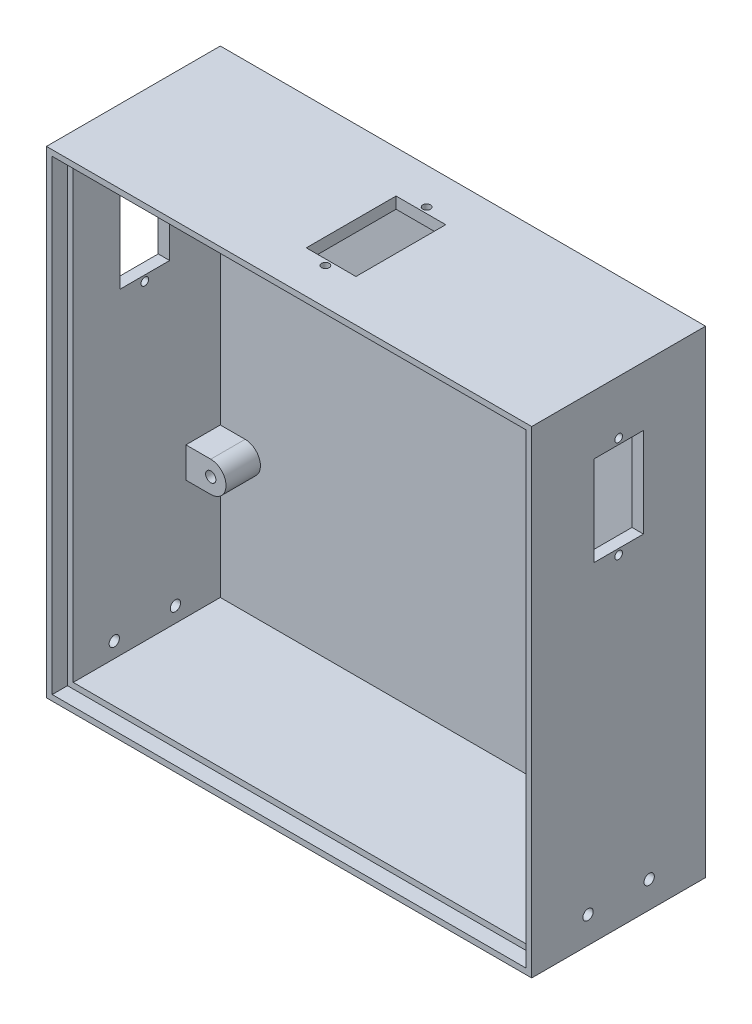
SolidWorks part; units mm, degrees
ref_plane "Front Plane" through (0, 0, 0) normal (0, 0, 1) x (1, 0, 0)
ref_plane "Top Plane" through (0, 0, 0) normal (0, 1, 0) x (1, 0, 0)
ref_plane "Right Plane" through (0, 0, 0) normal (1, 0, 0) x (0, 0, -1)
sketch "Sketch1" plane through (0, 0, 0) normal (0, 0, 1) x (1, 0, 0)
  line L1 (63.5, 62.5) -> (-63.5, 62.5)
  line L2 (63.5, 62.5) -> (63.5, -62.5)
  line L3 (63.5, -62.5) -> (-63.5, -62.5)
  line L4 (-63.5, 62.5) -> (-63.5, -62.5)
  line L5 (63.5, 62.5) -> (-63.5, -62.5) construction
  line L6 (63.5, -62.5) -> (-63.5, 62.5) construction
  point P0 (0, 0)
  dimension "D1" = 127
  dimension "D2" = 125
extrude "Boss-Extrude1" add sketch "Sketch1" along normal blind 45.5
sketch "Sketch2" plane through (0, 0, 45.5) normal (0, 0, 1) x (1, 0, 0)
  line L0 (-63.5, 62.5) -> (-63.5, -62.5) construction
  line L1 (60.5, 59.5) -> (-60.5, 59.5)
  line L2 (60.5, 59.5) -> (60.5, -59.5)
  line L3 (60.5, -59.5) -> (-60.5, -59.5)
  line L4 (-60.5, 59.5) -> (-60.5, -59.5)
  line L5 (60.5, 59.5) -> (-60.5, -59.5) construction
  line L6 (60.5, -59.5) -> (-60.5, 59.5) construction
  line L7 (63.5, 62.5) -> (-63.5, 62.5) construction
  line L9 (62, 61) -> (-62, 61)
  line L10 (62, 61) -> (62, -61)
  line L11 (62, -61) -> (-62, -61)
  line L12 (-62, 61) -> (-62, -61)
  line L13 (62, 61) -> (-62, -61) construction
  line L14 (62, -61) -> (-62, 61) construction
  point P0 (0, 0)
  point P10 (0, 0)
  dimension "D1" = 3
  dimension "D2" = 3
  dimension "D3" = 1.5
  dimension "D4" = 1.5
extrude "Cut-Extrude1" cut sketch "Sketch2" against normal offset from surface (42.5 mm away) 3 contours L1 L4 L3 L2 region at (0, 0, 45.5) up to face at (0, 0, 0)
extrude "Cut-Extrude2" cut sketch "Sketch2<3>" against normal blind 4
sketch "Sketch2<3>" plane through (0, 0, 45.5) normal (0, 0, 1) x (1, 0, 0) same geometry as "Sketch2"
sketch "Sketch3" plane through (0, 0, 3) normal (0, 0, 1) x (1, 0, 0)
  line L0 (35, 53) -> (35, 59.5)
  line L1 (60.5, 59.5) -> (-60.5, 59.5) construction
  line L2 (43, 53) -> (43, 59.5)
  line L3 (60.5, 59.5) -> (-60.5, 59.5) construction
  line L4 (0, -25.025) -> (0, 25.025) construction
  arc A0 (35, 53) -> (43, 53) centre (39, 53) ccw
  circle A2 centre (39, 53) radius 1.35
  line M3 (60.5, 59.5) -> (-60.5, 59.5)
  dimension "D2" = 4
  dimension "D3" = 2.7
  dimension "D1" = 6.5
  dimension "D4" = 39
extrude "Boss-Extrude2" add sketch "Sketch3" along normal blind 9 contours L0 A0 L2 A2 M3 region at (39, 54.7692, 3)
mirror "Mirror1" about plane through (0, 0, 0) normal (1, 0, 0) of "Boss-Extrude2"
sketch "Sketch4" plane through (0, 0, 3) normal (0, 0, 1) x (1, 0, 0)
  line L0 (54, -20.4) -> (60.5, -20.4)
  line L1 (60.5, 59.5) -> (60.5, -59.5) construction
  line L2 (54, -28.4) -> (60.5, -28.4)
  arc A0 (54, -20.4) -> (54, -28.4) centre (54, -24.4) ccw
  circle A1 centre (54, -24.4) radius 1.35
  circle A2 centre (39, 53) radius 1.35 construction
  line M9 (60.5, -59.5) -> (60.5, 59.5)
  dimension "D2" = 4
  dimension "D3" = 2.7
  dimension "D4" = 77.4
  dimension "D1" = 6.5
extrude "Boss-Extrude3" add sketch "Sketch4" along normal blind 9 contours L0 A0 L2 A1 M9 region at (55.7692, -24.4, 3)
mirror "Mirror2" about plane through (0, 0, 0) normal (1, 0, 0) of "Boss-Extrude3"
sketch "Sketch5" plane through (0, 62.5, 0) normal (0, 1, 0) x (1, 0, 0)
  line L0 (0, -22.75) -> (6.5, -22.75) construction
  line L1 (6.5, -11) -> (-6.5, -11)
  line L2 (6.5, -11) -> (6.5, -34.5)
  line L3 (6.5, -34.5) -> (-6.5, -34.5)
  line L4 (-6.5, -11) -> (-6.5, -34.5)
  line L5 (6.5, -11) -> (-6.5, -34.5) construction
  line L6 (6.5, -34.5) -> (-6.5, -11) construction
  line L7 (63.5, -45.5) -> (63.5, 0) construction
  circle A0 centre (0, -9.5) radius 1
  circle A1 centre (0, -36) radius 1
  point P0 (0, -22.75)
  point P8 (0, -11)
  point P12 (63.5, -22.75)
  dimension "D3" = 2
  dimension "D1" = 13
  dimension "D2" = 23.5
  dimension "D4" = 1.5
extrude "Cut-Extrude5" cut sketch "Sketch5" against normal up to surface (3 mm away) up to face at (0, 59.5, 12.4167)
sketch "Sketch7" plane through (63.5, 0, 0) normal (1, 0, 0) x (0, 0, -1)
  line L0 (-45.5, 62.5) -> (0, 62.5) construction
  line L1 (-16.25, 47) -> (-29.25, 47)
  line L2 (-16.25, 47) -> (-16.25, 23.5)
  line L3 (-16.25, 23.5) -> (-29.25, 23.5)
  line L4 (-29.25, 47) -> (-29.25, 23.5)
  line L5 (-16.25, 47) -> (-29.25, 23.5) construction
  line L6 (-16.25, 23.5) -> (-29.25, 47) construction
  line L8 (-22.75, 35.25) -> (-16.25, 35.25) construction
  circle A0 centre (-22.75, 48.5) radius 1
  circle A1 centre (-22.75, 22) radius 1
  point P0 (-22.75, 35.25)
  point P7 (-22.75, 62.5)
  dimension "D4" = 2
  dimension "D1" = 23.5
  dimension "D2" = 27.25
  dimension "D3" = 13
  dimension "D5" = 1.5
extrude "Cut-Extrude6" cut sketch "Sketch7" against normal up to surface (3 mm away) up to face at (60.5, -12.2, 14.875)
mirror "Mirror4" about plane through (0, 0, 0) normal (1, 0, 0) of "Cut-Extrude6"
sketch "Sketch8" plane through (-63.5, 0, 0) normal (-1, 0, 0) x (0, 0, 1)
  line L0 (45.5, -62.5) -> (0, -62.5) construction
  line L1 (22.75, -62.5) -> (22.75, 23) construction
  circle A1 centre (14.75, -55.5) radius 1.35
  circle A2 centre (22.75, 22) radius 1 construction
  circle A4 centre (30.75, -55.5) radius 1.35
  point P4 (22.75, -62.5)
  dimension "D5" = 2.7
  dimension "D4" = 7
  dimension "D6" = 8
extrude "Cut-Extrude7" cut sketch "Sketch8" against normal up to surface (127 mm away) up to face at (63.5, 21, 22.75)
